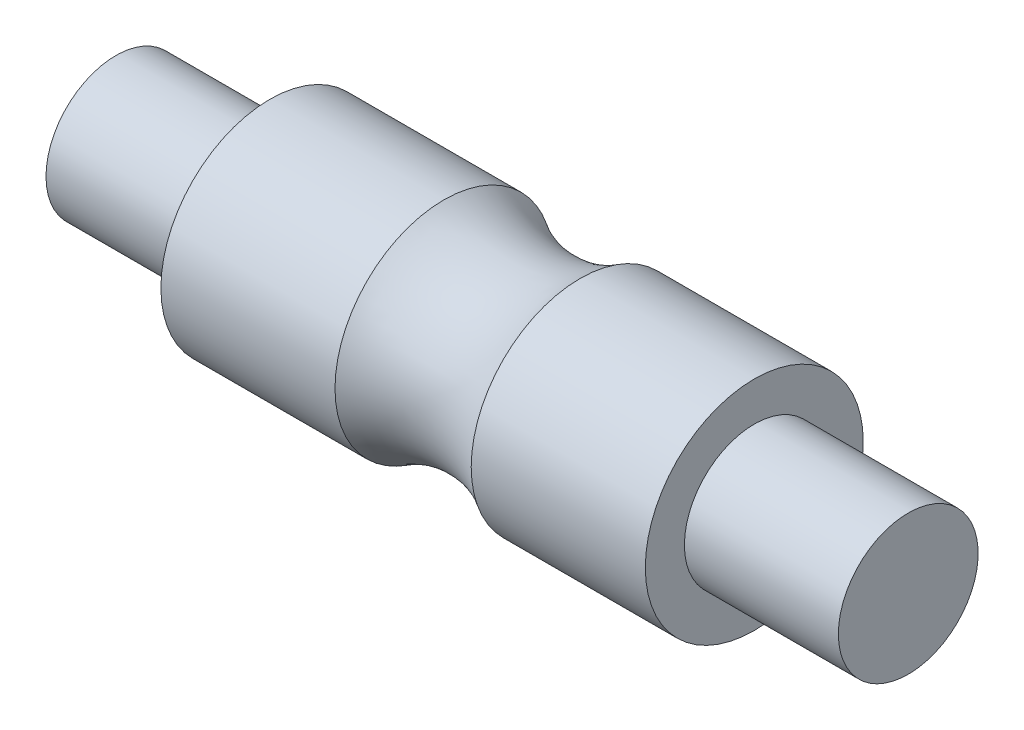
SolidWorks part; units mm, degrees
material "Chrome Stainless Steel"
ref_plane "Front Plane" through (0, 0, 0) normal (0, 0, 1) x (1, 0, 0)
ref_plane "Top Plane" through (0, 0, 0) normal (0, 1, 0) x (1, 0, 0)
ref_plane "Right Plane" through (0, 0, 0) normal (1, 0, 0) x (0, 0, -1)
ref_axis "X-axis" through (-88.99, 0, 0) along (1, 0, 0)
ref_axis "Y-axis" through (0, -55, 0) along (0, 1, 0)
ref_axis "Z-axis" through (0, 0, 55) along (0, 0, -1)
sketch "Sketch1" plane through (0, 0, 0) normal (0, 0, 1) x (1, 0, 0)
  line L0 (-9.9056, 0) -> (12.1876, 0) construction
  line L1 (0, 0) -> (8.4963, 0)
  line L2 (8.4963, 0) -> (8.4963, 1.4986)
  line L3 (8.4963, 1.4986) -> (5.1943, 1.4986)
  line L4 (5.1943, 1.4986) -> (5.1943, 2.3368)
  line L5 (5.1943, 2.3368) -> (1.4605, 2.3368)
  line L6 (0, 1.905) -> (0, 0)
  line L7 (0, 4.2978) -> (0, -4.9199) construction
  line L8 (-1.6418, 1.905) -> (-0.699, 1.905) construction
  arc A0 (1.4605, 2.3368) -> (0, 1.905) centre (0, 4.5909) cw
  dimension "D1" = 16.9926
  dimension "D2" = 2.9972
  dimension "D3" = 4.6736
  dimension "D4" = 3.81
  dimension "D5" = 2.921
  dimension "D6" = 10.3886
revolve "Revolve1" add sketch "Sketch1" angle 360 about L0
mirror "Mirror1" about plane through (0, 0, 0) normal (1, 0, 0) of "Revolve1"
